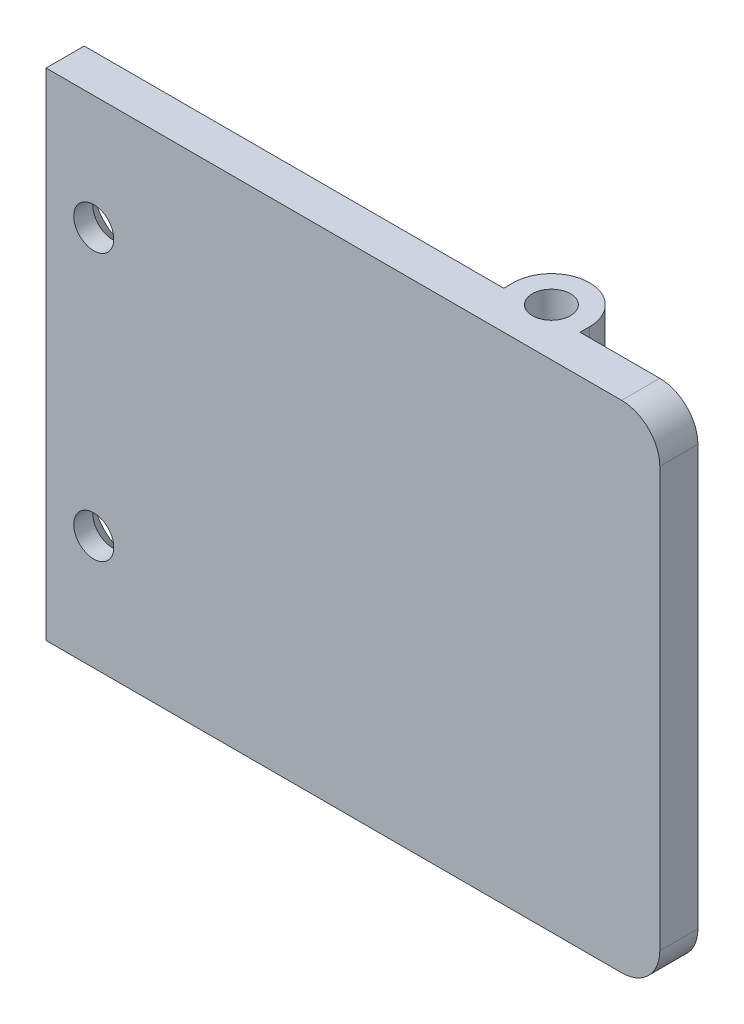
SolidWorks part; units mm, degrees
ref_plane "前视基准面" through (0, 0, 0) normal (0, 0, 1) x (1, 0, 0)
ref_plane "上视基准面" through (0, 0, 0) normal (0, 1, 0) x (1, 0, 0)
ref_plane "右视基准面" through (0, 0, 0) normal (1, 0, 0) x (0, 0, -1)
other "Configuration Table"
sketch "草图2" plane through (0, 0, 0) normal (0, 0, 1) x (1, 0, 0)
  line L1 (15.1907, -6.4342) -> (-16.9928, -6.4342)
  line L2 (15.1907, -6.4342) -> (15.1907, -32.4342)
  line L3 (15.1907, -32.4342) -> (-16.9928, -32.4342)
  line L4 (-16.9928, -6.4342) -> (-16.9928, -32.4342)
  line L6 (13.1907, -6.4342) -> (-12.8093, -6.4342) construction
  point P4 (0, 0)
  point P8 (0, 0)
  dimension "D1" = 32.1835
  dimension "D2" = 26
extrude "凸台-拉伸1" add sketch "草图2" along normal blind 2
fillet "圆角1" radius 2 2 edges at (15.1907, -32.4342, 1) (15.1907, -6.4342, 1)
sketch "草图4" plane through (0, 0, 0) normal (0, 0, -1) x (-1, 0, 0)
  line L0 (-13.1907, -6.4342) -> (16.9928, -6.4342) construction
  line L1 (16.9928, -6.4342) -> (16.9928, -32.4342) construction
  line L4 (16.9928, -32.4342) -> (-13.1907, -32.4342) construction
  circle A0 centre (14.4928, -12.4342) radius 1.05
  circle A1 centre (14.4928, -26.4342) radius 1.05
  dimension "D1" = 2.1
  dimension "D2" = 6
  dimension "D3" = 6
  dimension "D4" = 2.5
extrude "切除-拉伸2" cut sketch "草图4" against normal up to next
chamfer "倒角1" distance 1 angle 45 2 edges at (-15.5428, -12.4342, 0) (-15.5428, -26.4342, 0)
sketch "草图5" plane through (0, 0, 0) normal (0, 0, -1) x (-1, 0, 0)
  line L1 (-9.0072, -6.4342) -> (-5.0072, -6.4342)
  line L2 (-9.0072, -6.4342) -> (-9.0072, -8.4342)
  line L3 (-9.0072, -8.4342) -> (-5.0072, -8.4342)
  line L4 (-5.0072, -6.4342) -> (-5.0072, -8.4342)
  line L5 (16.9928, -32.4342) -> (-13.1907, -32.4342) construction
  line L6 (-9.0072, -32.4342) -> (-5.0072, -32.4342)
  line L7 (-9.0072, -32.4342) -> (-9.0072, -30.4342)
  line L8 (-9.0072, -30.4342) -> (-5.0072, -30.4342)
  line L9 (-5.0072, -32.4342) -> (-5.0072, -30.4342)
  line L11 (16.9928, -6.4342) -> (16.9928, -32.4342) construction
  line L12 (-13.1907, -6.4342) -> (16.9928, -6.4342) construction
  dimension "D1" = 2
  dimension "D2" = 22
  dimension "D3" = 4
extrude "凸台-拉伸2" add sketch "草图5" along normal blind 2.5
fillet "圆角2" radius 2 4 edges at (5.0072, -7.4342, -2.5) (9.0072, -7.4342, -2.5) (5.0072, -31.4342, -2.5) (9.0072, -31.4342, -2.5)
sketch "草图6" plane through (0, -32.4342, 0) normal (0, -1, 0) x (1, 0, 0)
  line L0 (5.0072, 0) -> (9.0072, 0) construction
  circle A0 centre (7.0072, 0) radius 1
  dimension "D1" = 2
extrude "切除-拉伸3" cut sketch "草图6" against normal blind 4 draft 2
sketch "草图7" plane through (0, -6.4342, 0) normal (0, 1, 0) x (1, 0, 0)
  circle A0 centre (7.0072, 0.5) radius 1
extrude "切除-拉伸4" cut sketch "草图7" against normal blind 4 draft 2
